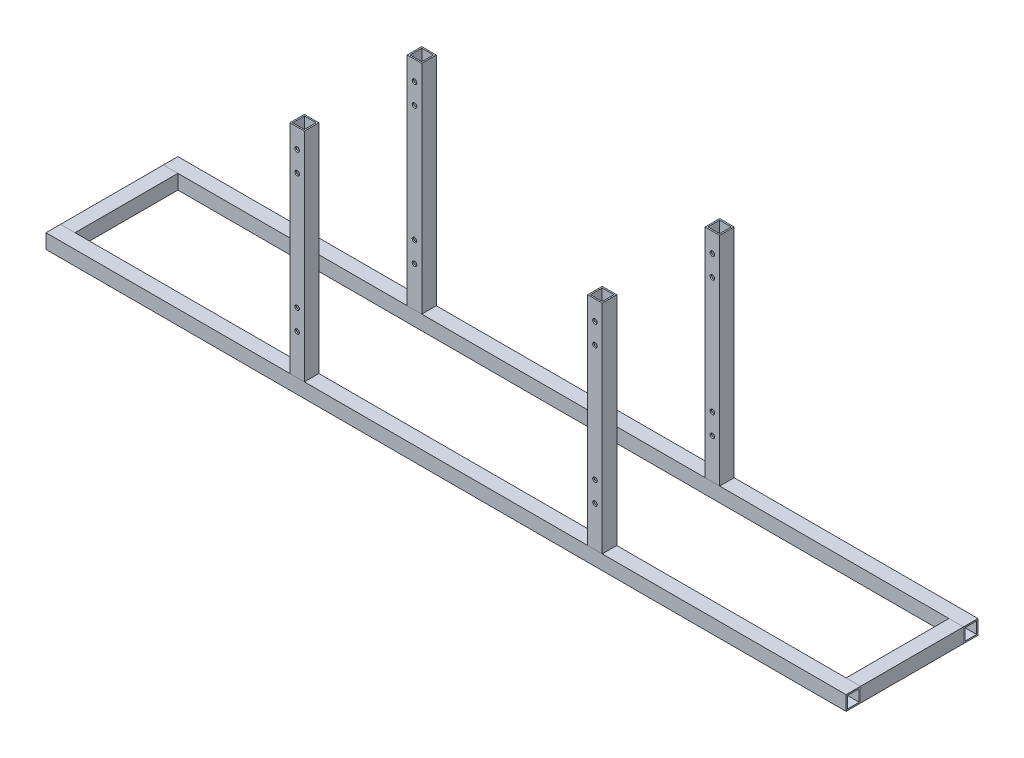
SolidWorks part; units mm, degrees
ref_plane "Front Plane" through (0, 0, 0) normal (0, 0, 1) x (1, 0, 0)
ref_plane "Top Plane" through (0, 0, 0) normal (0, 1, 0) x (1, 0, 0)
ref_plane "Right Plane" through (0, 0, 0) normal (1, 0, 0) x (0, 0, -1)
sketch "Sketch1" plane through (0, 0, 0) normal (0, 0, 1) x (1, 0, 0)
  line L0 (-337.3, 6.35) -> (-337.3, -6.35)
  line L1 (350, 6.35) -> (-350, 6.35)
  line L2 (350, 6.35) -> (350, -6.35)
  line L3 (350, -6.35) -> (-350, -6.35)
  line L4 (-350, 6.35) -> (-350, -6.35)
  line L5 (350, 6.35) -> (-350, -6.35) construction
  line L6 (350, -6.35) -> (-350, 6.35) construction
  line L7 (337.3, 6.35) -> (337.3, -6.35)
  point P0 (0, 0)
  dimension "D1" = 700
  dimension "D2" = 12.7
  dimension "D3" = 12.7
  dimension "D4" = 12.7
extrude "Boss-Extrude1" add sketch "Sketch1" along normal mid plane 90 contours L1 L4 L3 L0 | L1 L7 L3 L2 region at (-343.65, 0, 0) region at (343.65, 0, 0)
shell "Shell1" thickness 1.2 removed face at (-343.65, 0, -45) removed face at (-343.65, 0, 45)
shell "Shell2" thickness 1.2 removed face at (343.65, 0, 45) removed face at (343.65, 0, -45)
extrude "Boss-Extrude2" add sketch "Sketch1<3>" along normal blind 12.7 from surface separate body contours L7 L1 L0 L3 | L1 L4 L3 L0 | L1 L7 L3 L2 region at (0, 0, 0) region at (-343.65, 0, 0) region at (343.65, 0, 0) starting at face at (343.65, 0, 45)
sketch "Sketch1<3>" plane through (0, 0, 0) normal (0, 0, 1) x (1, 0, 0) same geometry as "Sketch1"
shell "Shell3" thickness 1.2 removed face at (-350, 0, 51.35) removed face at (350, 0, 51.35)
mirror "Mirror1" about plane through (0, 0, 0) normal (0, 0, 1) of bodies 103
sketch "Sketch3" plane through (0, 0, 0) normal (0, 1, 0) x (1, 0, 0)
  line L0 (-350, -57.7) -> (350, -57.7) construction
  line L1 (-136.65, -57.7) -> (-123.95, -57.7)
  line L2 (-136.65, -57.7) -> (-136.65, -45)
  line L3 (-136.65, -45) -> (-123.95, -45)
  line L4 (-123.95, -57.7) -> (-123.95, -45)
  line L5 (-350, -45) -> (350, -45) construction
  line L6 (-350, 45) -> (350, 45) construction
  line L7 (-136.65, 45) -> (-123.95, 45)
  line L8 (-136.65, 45) -> (-136.65, 57.7)
  line L9 (-136.65, 57.7) -> (-123.95, 57.7)
  line L10 (-123.95, 45) -> (-123.95, 57.7)
  line L11 (-350, 57.7) -> (350, 57.7) construction
  line L12 (0, -6.985) -> (0, 6.985) construction
  line L13 (123.95, 45) -> (123.95, 57.7)
  line L14 (136.65, 57.7) -> (123.95, 57.7)
  line L15 (136.65, 45) -> (136.65, 57.7)
  line L16 (136.65, 45) -> (123.95, 45)
  line L17 (123.95, -57.7) -> (123.95, -45)
  line L18 (136.65, -45) -> (123.95, -45)
  line L19 (136.65, -57.7) -> (136.65, -45)
  line L20 (136.65, -57.7) -> (123.95, -57.7)
  point P16 (-130.3, 45)
  dimension "D1" = 12.7
  dimension "D2" = 130.3
extrude "Extrude-Thin1" add sketch "Sketch3" along normal blind 190 from surface separate body thin starting at face at (0, 6.35, 51.35) thin type one direction reverse wall 1.2
sketch "Sketch4" plane through (0, 0, 0) normal (0, 0, 1) x (1, 0, 0)
  line L0 (-123.95, 6.35) -> (-136.65, 6.35) construction
  line L1 (0, -6.985) -> (0, 6.985) construction
  circle A0 centre (-130.3, 41.35) radius 2
  circle A1 centre (-130.3, 59.35) radius 2
  circle A2 centre (-130.3, 179.35) radius 2
  circle A3 centre (-130.3, 161.35) radius 2
  circle A4 centre (130.3, 161.35) radius 2
  circle A5 centre (130.3, 179.35) radius 2
  circle A6 centre (130.3, 59.35) radius 2
  circle A7 centre (130.3, 41.35) radius 2
  point P5 (-130.3, 6.35)
  dimension "D1" = 4
  dimension "D3" = 4
  dimension "D2" = 35
  dimension "D4" = 18
  dimension "D6" = 120
  dimension "D5" = 2
extrude "Cut-Extrude1" cut sketch "Sketch4" against normal through all both and the other way through all
